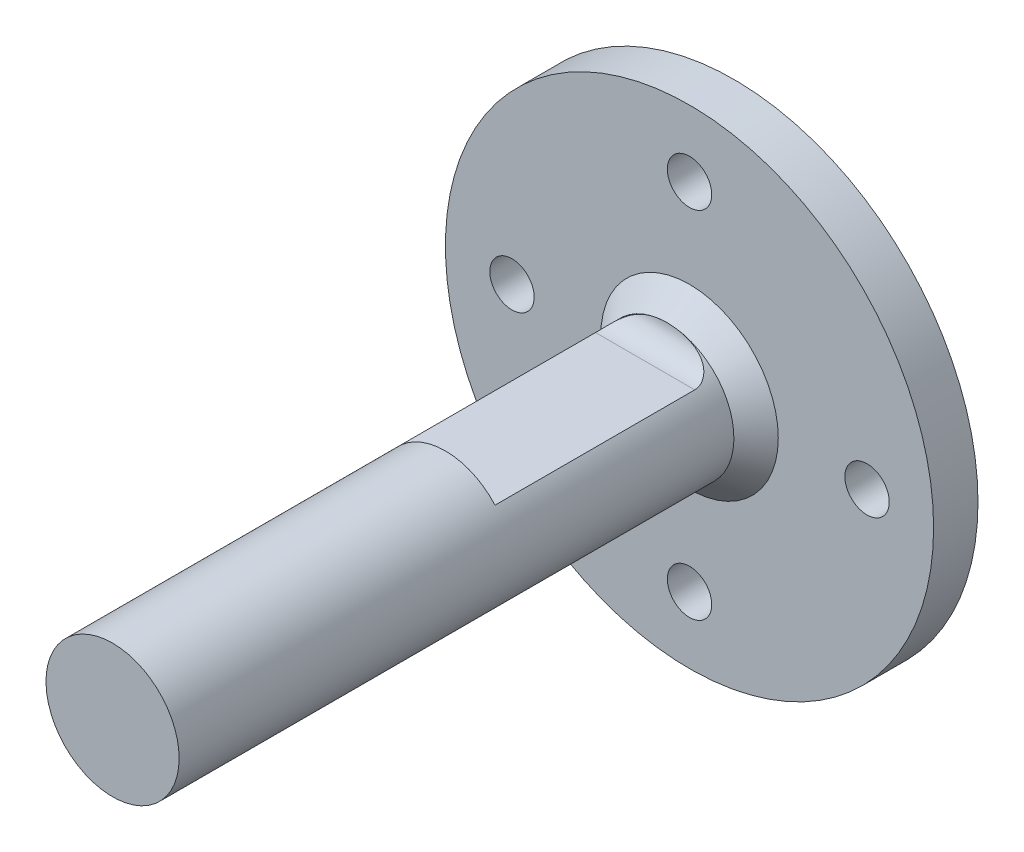
SolidWorks part; units mm, degrees
other "Uwaga1"
sketch "Szkic4" plane through (11, 11, 28) normal (0.6275, 0.305, 0.7164) x (0.6868, 0.2167, -0.6938)
sketch "Szkic5" plane through (11, 11, 28) normal (0.6275, 0.305, 0.7164) x (0.6868, 0.2167, -0.6938)
sketch "Szkic7" plane through (11, 11, 28) normal (0.6275, 0.305, 0.7164) x (0.6868, 0.2167, -0.6938)
sketch "Szkic9" plane through (11, 11, 28) normal (0.6275, 0.305, 0.7164) x (0.6868, 0.2167, -0.6938)
other "Uwaga2"
sketch "Szkic6" plane through (11, 11, 28) normal (0.4562, 0.5282, 0.7161) x (0.8246, 0.0515, -0.5633)
sketch "Szkic8" plane through (11, 11, 28) normal (0.4562, 0.5282, 0.7161) x (0.8246, 0.0515, -0.5633)
sketch "Szkic10" plane through (11, 11, 28) normal (0.4562, 0.5282, 0.7161) x (0.8246, 0.0515, -0.5633)
material "Chromowa stal nierdzewna"
ref_plane "Płaszczyzna przednia" through (0, 0, 0) normal (0, 0, 1) x (1, 0, 0)
ref_plane "Płaszczyzna górna" through (0, 0, 0) normal (0, 1, 0) x (1, 0, 0)
ref_plane "Płaszczyzna prawa" through (0, 0, 0) normal (1, 0, 0) x (0, 0, -1)
sketch "Szkic1" plane through (0, 0, 0) normal (0, 0, 1) x (1, 0, 0)
  circle A0 centre (0, 0) radius 11
  circle A1 centre (0, 8) radius 1
  circle A2 centre (8, 0) radius 1
  circle A3 centre (0, -8) radius 1
  circle A4 centre (-8, 0) radius 1
  point P14 (0, 0)
  dimension "D1" = 22
  dimension "D2" = 2
  dimension "D3" = 8
  dimension "D4" = 4
extrude "Dodanie-wyciągnięcie1" add sketch "Szkic1" along normal blind 2
sketch "Szkic2" plane through (0, 0, 2) normal (0, 0, 1) x (1, 0, 0)
  circle A0 centre (0, 0) radius 3
  dimension "D1" = 6
extrude "Dodanie-wyciągnięcie2" add sketch "Szkic2" along normal blind 26
sketch "Szkic3" plane through (0, 0, 28) normal (0, 0, 1) x (1, 0, 0)
  line L0 (-2.2361, 2) -> (2.2361, 2)
  arc A3 (2.2361, 2) -> (-2.2361, 2) centre (0, 0) ccw
  dimension "D1" = 2
extrude "Wytnij-wyciągnięcie1" cut sketch "Szkic3" against normal blind 10 from offset 15 offset against normal yes
chamfer "Sfazowanie1" distance 1 angle 45 1 edges at (3, 0, 2)
fillet "Zaokrąglenie1" radius 1 1 edges at (0, 2, 3)
